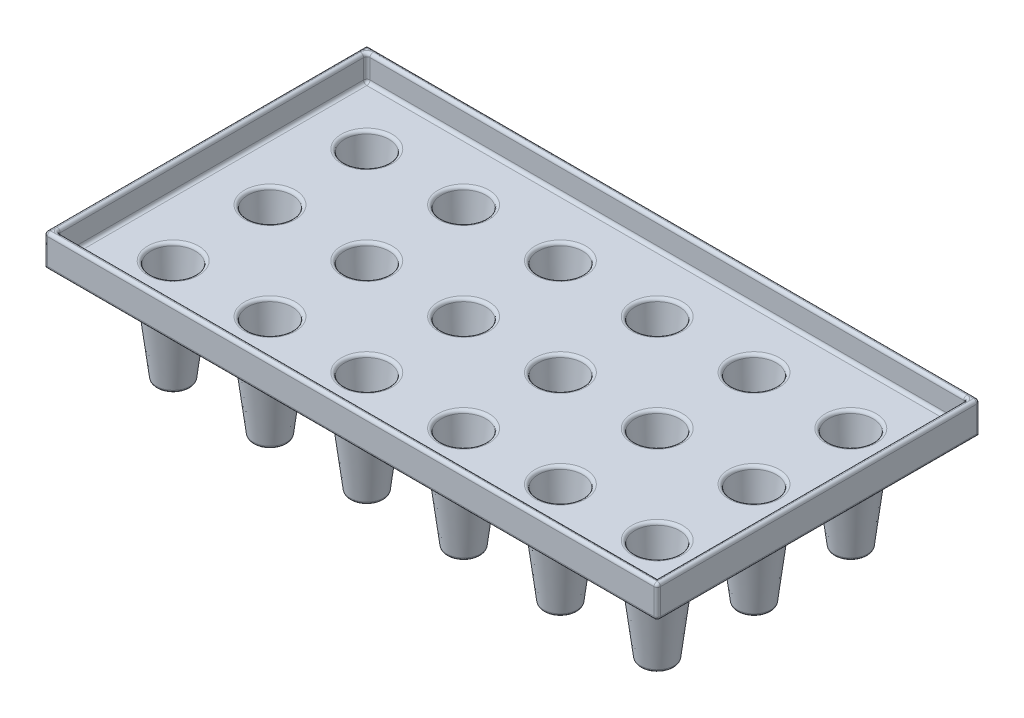
SolidWorks part; units mm, degrees
ref_plane "Front Plane" through (0, 0, 0) normal (0, 0, 1) x (1, 0, 0)
ref_plane "Top Plane" through (0, 0, 0) normal (0, 1, 0) x (1, 0, 0)
ref_plane "Right Plane" through (0, 0, 0) normal (1, 0, 0) x (0, 0, -1)
sketch "Sketch1" plane through (0, 0, 0) normal (0, 1, 0) x (1, 0, 0)
  line L1 (0, 0) -> (-241.3, 0)
  line L2 (0, 0) -> (0, 127)
  line L3 (0, 127) -> (-241.3, 127)
  line L4 (-241.3, 0) -> (-241.3, 127)
  dimension "D1" = 127
  dimension "D2" = 241.3
extrude "Boss-Extrude1" add sketch "Sketch1" against normal blind 12.7
sketch "Sketch2" plane through (0, 0, 0) normal (0, 1, 0) x (1, 0, 0)
  line L0 (-241.3, 127) -> (-241.3, 0) construction
  line L1 (-241.3, 0) -> (0, 0) construction
  circle A0 centre (-215.9, 25.4) radius 12.7
  dimension "D1" = 25.4
  dimension "D2" = 25.4
  dimension "D3" = 25.4
extrude "Boss-Extrude2" add sketch "Sketch2" against normal blind 50.8 draft 7
pattern_linear "LPattern1" count 6 spacing 38.1 along (1, 0, 0) count 3 spacing 38.1 along (0, 0, -1) of "Boss-Extrude2"
shell "Shell1" thickness 2.54 removed face at (-120.65, 0, -63.5)
fillet "Fillet1" radius 1.27 92 edges at (-177.8, -10.16, -16.5066) (-177.8, -48.26, -21.1847) (-215.9, -48.26, -21.1847) (-215.9, -10.16, -16.5066) (-2.54, 0, -63.5) (-120.65, 0, -124.46) (-238.76, 0, -63.5) (-120.65, 0, -2.54) (-2.54, -10.16, -63.5) (-120.65, -10.16, -124.46) (-238.76, -10.16, -63.5) (-120.65, -10.16, -2.54) (-2.54, -5.08, -124.46) (-238.76, -5.08, -124.46) (-238.76, -5.08, -2.54) (-139.7, -10.16, -16.5066) (-139.7, -48.26, -21.1847) (-101.6, -10.16, -16.5066) (-101.6, -48.26, -21.1847) (-63.5, -10.16, -16.5066) (-63.5, -48.26, -21.1847) (-25.4, -10.16, -16.5066) (-25.4, -48.26, -21.1847) (-215.9, -10.16, -54.6066) (-215.9, -48.26, -59.2847) (-177.8, -10.16, -54.6066) (-177.8, -48.26, -59.2847) (-139.7, -10.16, -54.6066) (-139.7, -48.26, -59.2847) (-101.6, -10.16, -54.6066) (-101.6, -48.26, -59.2847) (-63.5, -10.16, -54.6066) (-63.5, -48.26, -59.2847) (-25.4, -10.16, -54.6066) (-25.4, -48.26, -59.2847) (-215.9, -10.16, -92.7066) (-215.9, -48.26, -97.3847) (-177.8, -10.16, -92.7066) (-177.8, -48.26, -97.3847) (-139.7, -10.16, -92.7066) (-139.7, -48.26, -97.3847) (-101.6, -10.16, -92.7066) (-101.6, -48.26, -97.3847) (-63.5, -10.16, -92.7066) (-63.5, -48.26, -97.3847) (-25.4, -10.16, -92.7066) (-25.4, -48.26, -97.3847) (-177.8, -12.7, -14.2594) (-177.8, -50.8, -18.9375) (-215.9, -50.8, -18.9375) (-215.9, -12.7, -14.2594) (0, 0, -63.5) (-120.65, 0, -127) (-241.3, 0, -63.5) (-120.65, 0, 0) (0, -12.7, -63.5) (-120.65, -12.7, 0) (0, -6.35, -127) (-241.3, -6.35, 0) (0, -6.35, 0) (-139.7, -12.7, -14.2594) (-139.7, -50.8, -18.9375) (-101.6, -12.7, -14.2594) (-101.6, -50.8, -18.9375) (-63.5, -12.7, -14.2594) (-63.5, -50.8, -18.9375) (-25.4, -12.7, -14.2594) (-25.4, -50.8, -18.9375) (-215.9, -12.7, -52.3594) (-215.9, -50.8, -57.0375) (-177.8, -12.7, -52.3594) (-177.8, -50.8, -57.0375) (-139.7, -12.7, -52.3594) (-139.7, -50.8, -57.0375) (-101.6, -12.7, -52.3594) (-101.6, -50.8, -57.0375) (-63.5, -12.7, -52.3594) (-63.5, -50.8, -57.0375) (-25.4, -12.7, -52.3594) (-25.4, -50.8, -57.0375) (-215.9, -12.7, -90.4594) (-215.9, -50.8, -95.1375) (-177.8, -12.7, -90.4594) (-177.8, -50.8, -95.1375) (-139.7, -12.7, -90.4594) (-139.7, -50.8, -95.1375) (-101.6, -12.7, -90.4594) (-101.6, -50.8, -95.1375) (-63.5, -12.7, -90.4594) (-63.5, -50.8, -95.1375) (-25.4, -12.7, -90.4594) (-25.4, -50.8, -95.1375)
